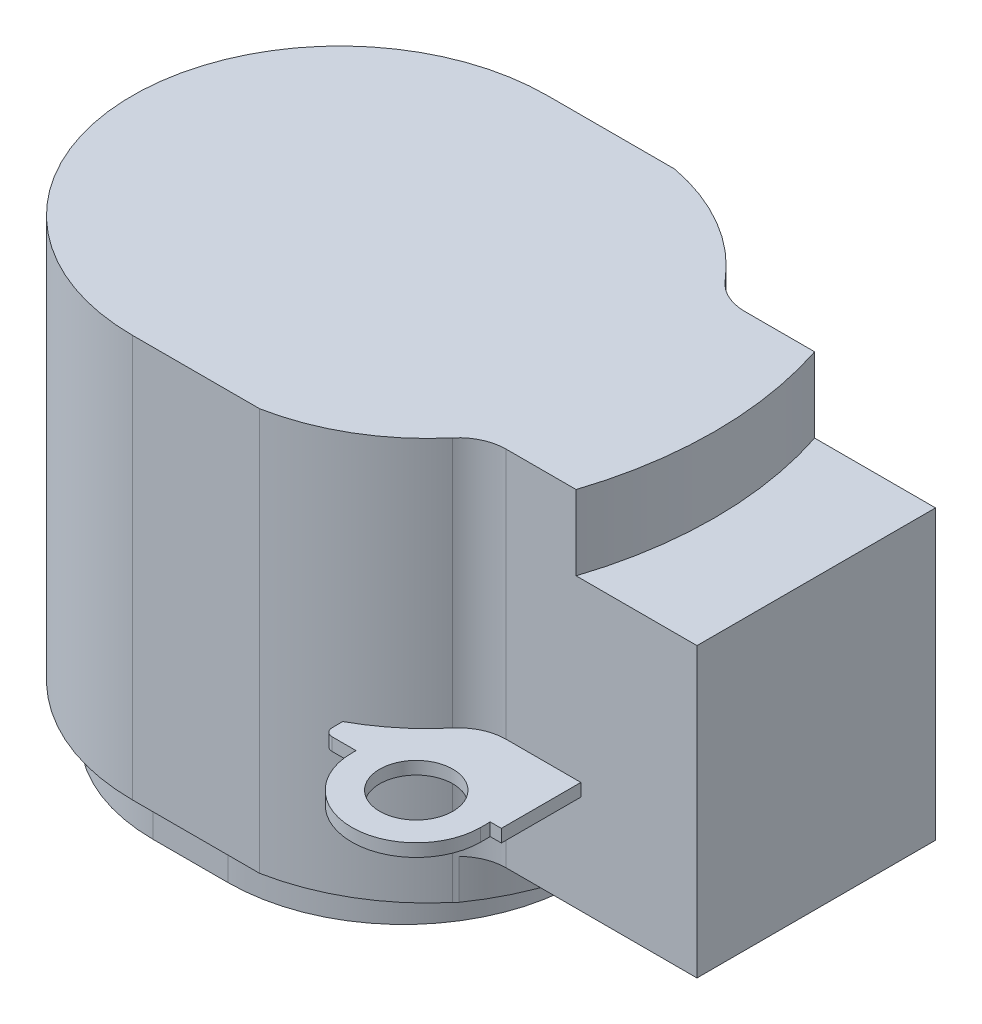
SolidWorks part; units mm, degrees
ref_plane "Front Plane" through (0, 0, 0) normal (0, 0, 1) x (1, 0, 0)
ref_plane "Top Plane" through (0, 0, 0) normal (0, 1, 0) x (1, 0, 0)
ref_plane "Right Plane" through (0, 0, 0) normal (1, 0, 0) x (0, 0, -1)
sketch "Sketch1" plane through (0, 0, 0) normal (0, 1, 0) x (1, 0, 0)
  line L5 (-4, 0) -> (1.4987, 0) construction
  line L6 (-4, 13.05) -> (4, 13.05)
  line L14 (-4, -13.05) -> (4, -13.05)
  line L16 (25.95, 7.5) -> (13.95, 7.5)
  line L17 (25.95, 7.5) -> (25.95, -7.5)
  line L18 (25.95, -7.5) -> (13.95, -7.5)
  arc A7 (-4, 13.05) -> (-4, -13.05) centre (-4, 0) ccw
  arc A8 (4, -13.05) -> (11.6566, -8.566) centre (1.4987, 0) ccw
  arc A9 (11.6566, 8.566) -> (4, 13.05) centre (1.4987, 0) ccw
  arc A10 (13.95, -7.5) -> (11.6566, -8.566) centre (13.95, -10.5) ccw
  arc A11 (13.95, 7.5) -> (11.6566, 8.566) centre (13.95, 10.5) cw
  point P2 (0, 0)
  point P11 (25.95, 0)
  point P17 (12.4673, 7.5)
  point P18 (-17.05, 0)
  dimension "D1" = 26.1
  dimension "D5" = 3
  dimension "D4" = 12
  dimension "D2" = 8
  dimension "D3" = 15
  dimension "D6" = 43
extrude "Boss-Extrude1" add sketch "Sketch1" against normal blind 28.8
sketch "Sketch2" plane through (0, 0, 0) normal (0, 1, 0) x (1, 0, 0)
  line L0 (0, 0) -> (-4.7, 0) construction
  line L1 (0, -9.05) -> (-4.7, -9.05)
  line L2 (0, 9.05) -> (-4.7, 9.05)
  arc A1 (0, -9.05) -> (0, 9.05) centre (0, 0) ccw
  arc A2 (-4.7, 9.05) -> (-4.7, -9.05) centre (-4.7, 0) ccw
  arc A4 (-4, 13.05) -> (-4, -13.05) centre (-4, 0) ccw construction
  point P3 (-2.35, 0)
  point P9 (-13.75, 0)
  point P17 (-17.05, 0)
  dimension "D1" = 3.3
  dimension "D2" = 18.1
extrude "Cut-Extrude1" cut sketch "Sketch2" against normal through all
sketch "Sketch7" plane through (0, 0, 0) normal (0, 1, 0) x (1, 0, 0)
  line L0 (-4.7, 0) -> (0, 0) construction
  line L1 (-4.7, 10.05) -> (0, 10.05)
  line L2 (-4.7, -10.05) -> (0, -10.05)
  line L3 (0, 9.05) -> (-4.7, 9.05) construction
  arc A0 (-4.7, 10.05) -> (-4.7, -10.05) centre (-4.7, 0) ccw
  arc A1 (0, -10.05) -> (0, 10.05) centre (0, 0) ccw
  point P4 (-2.35, 0)
  dimension "D1" = 1
extrude "Boss-Extrude3" add sketch "Sketch7" against normal blind 1
sketch "Sketch3" plane through (0, 0, 0) normal (0, 1, 0) x (1, 0, 0)
  line L1 (25.95, 7.5) -> (18.35, 7.5)
  line L2 (25.95, 7.5) -> (25.95, -7.5)
  line L3 (25.95, -7.5) -> (18.35, -7.5)
  line L6 (25.95, -7.5) -> (25.95, 7.5) construction
  arc A0 (18.35, 7.5) -> (18.35, -7.5) centre (-4.4875, 0) cw
  point P8 (19.55, 0)
  dimension "D2" = 1.2
  dimension "D1" = 7.6
extrude "Cut-Extrude2" cut sketch "Sketch3" against normal blind 4.7
ref_plane "Plane1" through (0, -15.8, 0) normal (0, 1, 0) x (1, 0, 0)
sketch "Sketch4" plane through (0, -15.8, 0) normal (0, 1, 0) x (1, 0, 0)
  line L0 (13.9, 13.1) -> (13.9, -13.1) construction
  line L1 (17.95, 13.1) -> (17.95, -13.1)
  line L2 (9.85, 13.1) -> (9.85, -13.1)
  line L4 (13.9, 0) -> (-21.7278, 0) construction
  line L5 (9.85, 12.8351) -> (8.35, 12.8351)
  line L6 (9.85, 12.8351) -> (9.85, 10.1067)
  line L7 (9.85, 10.1067) -> (7.85, 10.1067)
  line L8 (7.85, 12.3351) -> (7.85, 10.1067)
  line L10 (17.95, 12.5) -> (18.65, 12.5)
  line L11 (17.95, 12.5) -> (17.95, 6.669)
  line L12 (17.95, 6.669) -> (18.65, 6.669)
  line L13 (18.65, 12.5) -> (18.65, 6.669)
  line L22 (18.65, -12.5) -> (18.65, -6.669)
  line L23 (17.95, -6.669) -> (18.65, -6.669)
  line L24 (17.95, -12.5) -> (17.95, -6.669)
  line L25 (17.95, -12.5) -> (18.65, -12.5)
  line L26 (7.85, -12.3351) -> (7.85, -10.1067)
  line L27 (9.85, -10.1067) -> (7.85, -10.1067)
  line L28 (9.85, -12.8351) -> (9.85, -10.1067)
  line L29 (9.85, -12.8351) -> (8.35, -12.8351)
  line L30 (25.95, -7.5) -> (25.95, 7.5) construction
  line L31 (25.95, 7.5) -> (18.35, 7.5) construction
  arc A0 (17.95, 13.1) -> (9.85, 13.1) centre (13.9, 13.1) ccw
  arc A1 (9.85, -13.1) -> (17.95, -13.1) centre (13.9, -13.1) ccw
  circle A2 centre (13.9, 13.1) radius 2.3
  circle A3 centre (13.9, -13.1) radius 2.3
  arc A5 (8.35, 12.8351) -> (7.85, 12.3351) centre (8.35, 12.3351) ccw
  arc A6 (8.35, -12.8351) -> (7.85, -12.3351) centre (8.35, -12.3351) cw
  arc A8 (11.6566, 8.566) -> (4, 13.05) centre (1.4987, 0) ccw construction
  point P2 (13.9, 0)
  point P9 (13.9, 17.15)
  point P10 (13.9, -17.15)
  point P23 (9.85, 10.3351)
  point P43 (7.85, 12.8351)
  point P45 (7.85, -12.8351)
  point P46 (9.85, -10.3351)
  dimension "D2" = 4.05
  dimension "D4" = 4.6
  dimension "D5" = 4.6
  dimension "D6" = 2.5
  dimension "D10" = 0.5
  dimension "D3" = 34.3
  dimension "D7" = 2
  dimension "D8" = 8
  dimension "D9" = 0.7
  dimension "D11" = 5
extrude "Boss-Extrude2" add sketch "Sketch4" against normal blind 0.8 contours L26 A1 L1 A0 L6 L2 A3 A2 | L5 L8 L7 L2 L6 | L13 L10 L1 L12 | L1 L25 L22 L23 | L26 L2 A6 region at (13.9, -15.8, 0) region at (18.3, -15.8, -9.5845) region at (8.8588, -15.8, -11.4585) region at (18.3, -15.8, 9.5845) region at (8.8588, -15.8, 11.4585)
sketch "Sketch5" plane through (0, -28.8, 0) normal (0, -1, 0) x (1, 0, 0)
  line L0 (-4.7, 0) -> (0, 0) construction
  line L1 (-4.7, 11.05) -> (0, 11.05)
  line L2 (-4.7, -11.05) -> (0, -11.05)
  line L3 (-4.7, 9.05) -> (0, 9.05) construction
  arc A0 (-4.7, 11.05) -> (-4.7, -11.05) centre (-4.7, 0) ccw
  arc A1 (0, -11.05) -> (0, 11.05) centre (0, 0) ccw
  point P4 (-2.35, 0)
  arc M5 (0, 9.05) -> (0, -9.05) centre (0, 0) cw
  line M6 (0, -9.05) -> (-4.7, -9.05)
  arc M7 (-4.7, -9.05) -> (-4.7, 9.05) centre (-4.7, 0) cw
  line M8 (-4.7, 9.05) -> (0, 9.05)
  dimension "D1" = 2
extrude "Cut-Extrude3" cut sketch "Sketch5" against normal blind 3.5 flip side to cut contours L2 A1 L1 A0 M8 M5 M6 M7 region at (-2.35, -28.8, 10.7026)
sketch "Sketch6" plane through (0, -25.3, 0) normal (0, -1, 0) x (1, 0, 0)
  line L0 (7.85, 12.3351) -> (7.85, 11.6713) construction
  line L2 (-0.9152, 14.4718) -> (-20.7495, 14.4718)
  line L4 (0, -14.5007) -> (-20.7495, -14.5007)
  line L5 (-20.7495, 14.4718) -> (-20.7495, -14.5007)
  arc A0 (0, -14.5007) -> (-0.9152, 14.4718) centre (0, 0) ccw
  arc A2 (11.6566, 8.566) -> (13.95, 7.5) centre (13.95, 10.5) ccw construction
  point P3 (11.85, 8.3576)
  dimension "D1" = 4
extrude "Cut-Extrude4" cut sketch "Sketch6" against normal blind 2.5 flip side to cut
sketch "Sketch8" plane through (25.95, 0, 0) normal (1, 0, 0) x (0, 0, -1)
  line L0 (-11.05, -28.8) -> (11.05, -28.8) construction
  line L1 (-3.42, -17.03) -> (3.42, -17.03)
  line L2 (-3.42, -17.03) -> (-3.42, -21.98)
  line L3 (-3.42, -21.98) -> (3.42, -21.98)
  line L4 (3.42, -17.03) -> (3.42, -21.98)
  line L5 (-3.42, -17.03) -> (3.42, -21.98) construction
  line L6 (-3.42, -21.98) -> (3.42, -17.03) construction
  line L7 (-3.42, -6.08) -> (3.42, -6.08)
  line L8 (-3.42, -6.08) -> (-3.42, -11.03)
  line L9 (-3.42, -11.03) -> (3.42, -11.03)
  line L10 (3.42, -6.08) -> (3.42, -11.03)
  line L11 (-3.42, -6.08) -> (3.42, -11.03) construction
  line L12 (-3.42, -11.03) -> (3.42, -6.08) construction
  point P0 (0, -19.505)
  point P5 (0, -8.555)
  dimension "D1" = 6.84
  dimension "D2" = 6.84
  dimension "D3" = 6.82
  dimension "D4" = 17.77
  dimension "D5" = 4.95
  dimension "D6" = 4.95
extrude "Boss-Extrude4" add sketch "Sketch8" against normal blind 25
